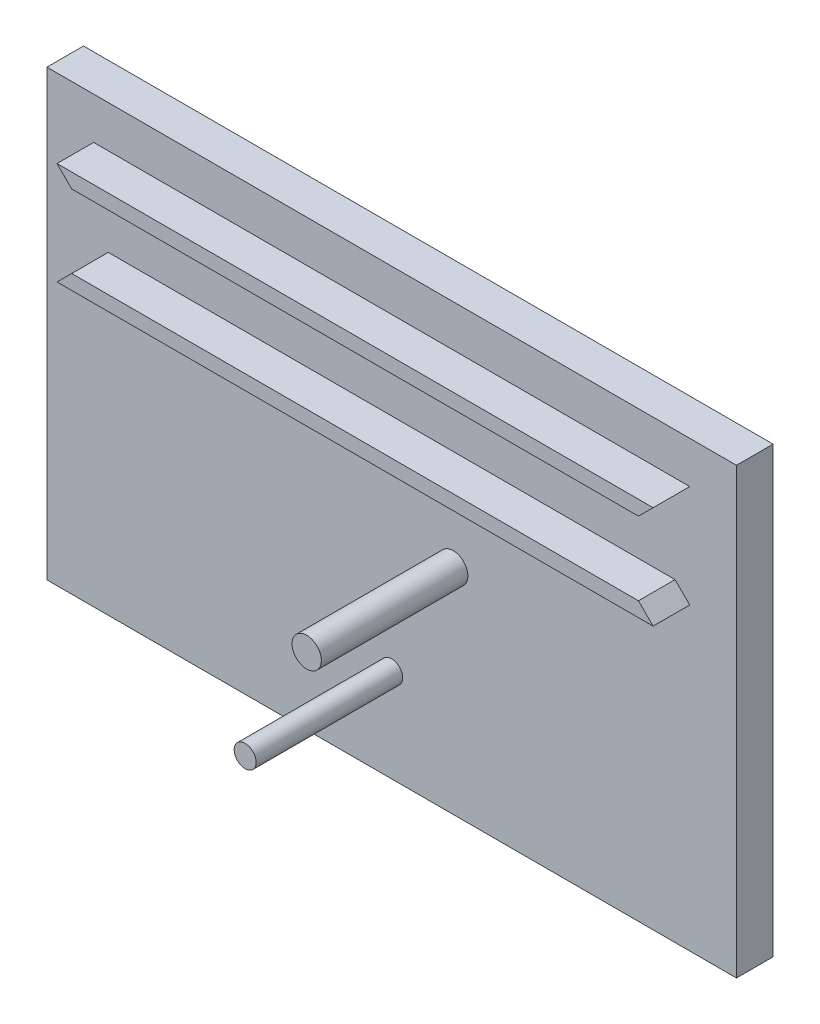
SolidWorks part; units mm, degrees
ref_plane "Front Plane" through (0, 0, 0) normal (0, 0, 1) x (1, 0, 0)
ref_plane "Top Plane" through (0, 0, 0) normal (0, 1, 0) x (1, 0, 0)
ref_plane "Right Plane" through (0, 0, 0) normal (1, 0, 0) x (0, 0, -1)
sketch "Sketch2" plane through (0, 0, 0) normal (0, 0, 1) x (1, 0, 0)
  line L0 (0, 0) -> (0, 89.408) construction
  line L1 (0, 0) -> (21.333, 41.8684) construction
  line L2 (0, 0) -> (53.1814, 0) construction
  line L3 (-98.2512, 102.108) -> (98.2512, 102.108)
  line L5 (-98.2512, 76.708) -> (98.2512, 76.708)
  line L7 (-98.2512, 102.108) -> (98.2512, 76.708) construction
  line L8 (-98.2512, 76.708) -> (98.2512, 102.108) construction
  line L9 (-103.3312, 71.628) -> (103.3312, 71.628)
  line L11 (-103.3312, 107.188) -> (103.3312, 107.188)
  line L13 (-98.2512, 102.108) -> (-98.2512, 76.708) construction
  line L14 (-103.3312, 107.188) -> (-103.3312, 71.628) construction
  line L15 (98.2512, 102.108) -> (98.2512, 76.708) construction
  line L16 (103.3312, 107.188) -> (103.3312, 71.628) construction
  line L17 (-103.3312, 71.628) -> (-98.2512, 76.708)
  line L18 (-103.3312, 107.188) -> (-98.2512, 102.108)
  line L19 (103.3312, 107.188) -> (98.2512, 102.108)
  line L20 (98.2512, 102.108) -> (98.2512, 76.708)
  line L21 (103.3312, 71.628) -> (98.2512, 76.708)
  line L23 (-119.5322, 121.6741) -> (119.5322, 121.6741)
  line L24 (-119.5322, 121.6741) -> (-119.5322, -32.2661)
  line L25 (-119.5322, -32.2661) -> (119.5322, -32.2661)
  line L26 (119.5322, 121.6741) -> (119.5322, -32.2661)
  line L27 (-119.5322, 121.6741) -> (119.5322, -32.2661) construction
  line L28 (-119.5322, -32.2661) -> (119.5322, 121.6741) construction
  circle A0 centre (0, 0) radius 3.81
  circle A1 centre (21.333, 41.8684) radius 5.08
  point P15 (0, 44.704)
  dimension "D6" = 10.16
  dimension "D7" = 7.62
  dimension "D1" = 89.408
  dimension "D2" = 46.99
  dimension "D3" = 63
  dimension "D4" = 25.4
  dimension "D8" = 153.9403
  dimension "D9" = 239.0644
  dimension "D10" = 196.5024
  dimension "D5" = 5.08
extrude "Boss-Extrude2" add sketch "Sketch2" along normal blind 12.7 contours L9 L21 L5 L17 | L19 L3 L18 L11 region at (0, 74.1467, 0)
extrude "Boss-Extrude3" add sketch "Sketch2<7>" against normal blind 12.7 contours L26 L23 L24 L25 A1 A0 L21 L9 L17 L5 L3 L18 L11 L19 | L19 L11 L18 L3 | L9 L21 L5 L17 | A0 | A1 region at (0, 104.6693, 0) region at (0, 74.1467, 0) region at (-0.0499, 42.1254, 0) region at (0, 0, 0)
sketch "Sketch2<7>" plane through (0, 0, 0) normal (0, 0, 1) x (1, 0, 0) same geometry as "Sketch2"
extrude "Boss-Extrude4" add sketch "Sketch2<8>" along normal blind 50.8 contours A1 | A0 region at (21.333, 41.8684, 0)
sketch "Sketch2<8>" plane through (0, 0, 0) normal (0, 0, 1) x (1, 0, 0) same geometry as "Sketch2"
